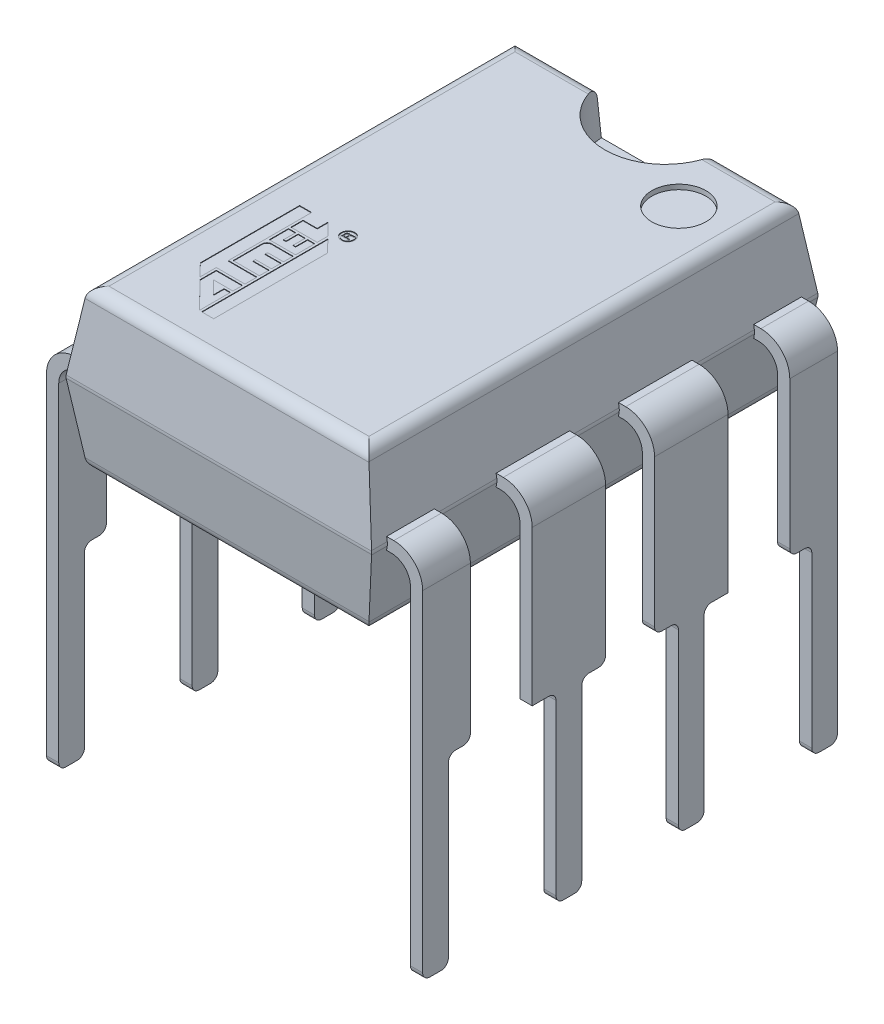
SolidWorks part; units mm, degrees
material "ABS"
ref_plane "Plano frontal" through (0, 0, 0) normal (0, 0, 1) x (1, 0, 0)
ref_plane "Plano superior" through (0, 0, 0) normal (0, 1, 0) x (1, 0, 0)
ref_plane "Plano direito" through (0, 0, 0) normal (1, 0, 0) x (0, 0, -1)
sketch "Esboço1" plane through (0, 0, 0) normal (0, 0, 1) x (1, 0, 0)
  line L0 (-3.175, 0) -> (3.175, 0) construction
  line L1 (3.1687, 0.0393) -> (2.9454, 1.4403)
  line L2 (2.6986, 1.651) -> (-2.6986, 1.651)
  line L3 (-2.9454, 1.4403) -> (-3.1687, 0.0393)
  line L4 (-3.1687, -0.0393) -> (-2.9454, -1.4403)
  line L5 (-2.6986, -1.651) -> (2.6986, -1.651)
  line L6 (3.1687, -0.0393) -> (2.9454, -1.4403)
  line L7 (-2.9119, -1.651) -> (-2.9119, 1.651) construction
  line L8 (2.9119, 1.651) -> (2.9119, -1.651) construction
  line L9 (2.9119, -1.651) -> (-2.9119, 1.651) construction
  line L10 (-2.9119, -1.651) -> (2.9119, 1.651) construction
  arc A0 (-2.6986, 1.651) -> (-2.9454, 1.4403) centre (-2.6986, 1.401) ccw
  arc A1 (-3.1687, -0.0393) -> (-3.1687, 0.0393) centre (-2.9218, 0) cw
  arc A2 (-2.9454, -1.4403) -> (-2.6986, -1.651) centre (-2.6986, -1.401) ccw
  arc A3 (2.6986, -1.651) -> (2.9454, -1.4403) centre (2.6986, -1.401) ccw
  arc A4 (3.1687, -0.0393) -> (3.1687, 0.0393) centre (2.9218, 0) ccw
  arc A5 (2.9454, 1.4403) -> (2.6986, 1.651) centre (2.6986, 1.401) ccw
  dimension "D3" = 0.25
  dimension "D1" = 6.35
  dimension "D2" = 3.302
  dimension "D4" = 5.8238
extrude "Ressalto-extrusão1" add sketch "Esboço1" along normal mid plane 9.271
sketch "Esboço2" plane through (0, 0, 0) normal (1, 0, 0) x (0, 0, -1)
  line L0 (0, 0) -> (6.8137, 0) construction
  line L1 (4.6319, 0.0301) -> (4.4621, 1.4311)
  line L2 (4.6355, -0.0393) -> (4.6355, 0.0393) construction
  line L3 (-4.6355, 1.651) -> (4.6355, 1.651) construction
  line L4 (4.214, 1.651) -> (3.6184, 1.651)
  line L5 (-4.6355, -1.651) -> (4.6355, -1.651) construction
  line L6 (4.4621, -1.4311) -> (4.6319, -0.0301)
  line L7 (3.6184, -1.651) -> (4.214, -1.651)
  line L8 (4.4355, 1.651) -> (5.0977, 1.651)
  line L9 (5.0977, 1.651) -> (5.0977, -1.651)
  line L10 (5.0977, -1.651) -> (4.4355, -1.651)
  line L11 (3.6184, 1.651) -> (3.6184, -1.651)
  line L13 (3.6184, 1.651) -> (5.0977, 1.651)
  line L14 (3.6184, 1.651) -> (3.6184, -1.651)
  line L15 (3.6184, -1.651) -> (5.0977, -1.651)
  line L16 (5.0977, 1.651) -> (5.0977, -1.651)
  arc A0 (4.4621, 1.4311) -> (4.214, 1.651) centre (4.214, 1.401) ccw
  arc A1 (4.6319, 0.0301) -> (4.6319, -0.0301) centre (4.3837, 0) cw
  arc A2 (4.214, -1.651) -> (4.4621, -1.4311) centre (4.214, -1.401) ccw
  point P20 (4.6355, 0)
  dimension "D1" = 0.25
  dimension "D2" = 0.6622
extrude "Corte-extrusão1" cut sketch "Esboço2" against normal through all both and the other way through all contours A1 L0 L9 L8 L13 A0 L1 | L0 A1 L6 A2 L15 L10 L16 region at (0, 0.8822, -4.8091) region at (0, -0.8822, -4.8091)
mirror "Espelhar1" about plane through (0, 0, 0) normal (0, 0, 1) of "Corte-extrusão1"
ref_plane "Plano1" through (0, 0, 1.27) normal (0, 0, 1) x (1, 0, 0)
sketch "Esboço3" plane through (0, 0, 1.27) normal (0, 0, 1) x (1, 0, 0)
  line L0 (-3.904, -7.495) -> (-3.904, -0.475)
  line L1 (-3.304, 0.125) -> (3.304, 0.125)
  line L2 (3.904, -0.475) -> (3.904, -7.495)
  line L3 (3.904, -7.495) -> (3.65, -7.495)
  line L4 (3.65, -7.495) -> (3.65, -0.525)
  line L5 (3.25, -0.125) -> (-3.25, -0.125)
  line L6 (-3.65, -0.525) -> (-3.65, -7.495)
  line L7 (-3.65, -7.495) -> (-3.904, -7.495)
  line L8 (0, -0.125) -> (0, 0.125) construction
  arc A0 (3.65, -0.525) -> (3.25, -0.125) centre (3.25, -0.525) ccw
  arc A1 (-3.25, -0.125) -> (-3.65, -0.525) centre (-3.25, -0.525) ccw
  arc A2 (3.304, 0.125) -> (3.904, -0.475) centre (3.304, -0.475) cw
  arc A3 (-3.904, -0.475) -> (-3.304, 0.125) centre (-3.304, -0.475) cw
  point P17 (3.904, 0.125)
  dimension "D5" = 0.4
  dimension "D6" = 0.6
  dimension "D1" = 0.254
  dimension "D2" = 0.25
  dimension "D3" = 7.3
  dimension "D4" = 7.62
extrude "Ressalto-extrusão2" add sketch "Esboço3" along normal mid plane 1.524
ref_plane "Plano2" through (0, 0, 3.81) normal (0, 0, 1) x (1, 0, 0)
sketch "Esboço4" plane through (0, 0, 3.81) normal (0, 0, 1) x (1, 0, 0)
  line L0 (3.1687, -0.0393) -> (3.1551, -0.125) construction
  line L1 (3.1551, -0.125) -> (3.25, -0.125) construction
  line L2 (3.65, -0.525) -> (3.65, -7.495) construction
  line L3 (3.65, -7.495) -> (3.904, -7.495) construction
  line L4 (3.904, -7.495) -> (3.904, -0.475) construction
  line L5 (3.304, 0.125) -> (3.1551, 0.125) construction
  line L6 (3.1551, 0.125) -> (3.1687, 0.0393) construction
  line L7 (-3.1687, 0.0393) -> (-3.1551, 0.125) construction
  line L8 (-3.1551, 0.125) -> (-3.304, 0.125) construction
  line L9 (-3.904, -0.475) -> (-3.904, -7.495) construction
  line L10 (-3.904, -7.495) -> (-3.65, -7.495) construction
  line L11 (-3.65, -7.495) -> (-3.65, -0.525) construction
  line L12 (-3.25, -0.125) -> (-3.1551, -0.125) construction
  line L13 (-3.1551, -0.125) -> (-3.1687, -0.0393) construction
  line L14 (3.1687, -0.0393) -> (3.1551, -0.125)
  line L15 (3.1551, -0.125) -> (3.25, -0.125)
  line L16 (3.65, -0.525) -> (3.65, -7.495)
  line L17 (3.65, -7.495) -> (3.904, -7.495)
  line L18 (3.904, -7.495) -> (3.904, -0.475)
  line L19 (3.304, 0.125) -> (3.1551, 0.125)
  line L20 (3.1551, 0.125) -> (3.1687, 0.0393)
  line L21 (-3.1687, 0.0393) -> (-3.1551, 0.125)
  line L22 (-3.1551, 0.125) -> (-3.304, 0.125)
  line L23 (-3.904, -0.475) -> (-3.904, -7.495)
  line L24 (-3.904, -7.495) -> (-3.65, -7.495)
  line L25 (-3.65, -7.495) -> (-3.65, -0.525)
  line L26 (-3.25, -0.125) -> (-3.1551, -0.125)
  line L27 (-3.1551, -0.125) -> (-3.1687, -0.0393)
  arc A0 (3.1687, -0.0393) -> (3.1687, 0.0393) centre (2.9218, 0) ccw construction
  arc A1 (3.65, -0.525) -> (3.25, -0.125) centre (3.25, -0.525) ccw construction
  arc A2 (3.904, -0.475) -> (3.304, 0.125) centre (3.304, -0.475) ccw construction
  arc A3 (-3.1687, 0.0393) -> (-3.1687, -0.0393) centre (-2.9218, 0) ccw construction
  arc A4 (-3.304, 0.125) -> (-3.904, -0.475) centre (-3.304, -0.475) ccw construction
  arc A5 (-3.25, -0.125) -> (-3.65, -0.525) centre (-3.25, -0.525) ccw construction
  arc A6 (3.1687, -0.0393) -> (3.1687, 0.0393) centre (2.9218, 0) ccw
  arc A7 (3.65, -0.525) -> (3.25, -0.125) centre (3.25, -0.525) ccw
  arc A8 (3.904, -0.475) -> (3.304, 0.125) centre (3.304, -0.475) ccw
  arc A9 (-3.1687, 0.0393) -> (-3.1687, -0.0393) centre (-2.9218, 0) ccw
  arc A10 (-3.304, 0.125) -> (-3.904, -0.475) centre (-3.304, -0.475) ccw
  arc A11 (-3.25, -0.125) -> (-3.65, -0.525) centre (-3.25, -0.525) ccw
extrude "Ressalto-extrusão3" add sketch "Esboço4" along normal mid plane 0.9906
mirror "Espelhar2" about plane through (0, 0, 0) normal (0, 0, 1) of "Ressalto-extrusão2", "Ressalto-extrusão3"
sketch "Esboço5" plane through (0, 0, 0) normal (1, 0, 0) x (0, 0, -1)
  line L0 (1.882, -3.683) -> (1.6867, -3.683)
  line L1 (2.032, -7.495) -> (2.032, -0.475) construction
  line L2 (1.5367, -3.833) -> (1.5367, -7.345)
  line L3 (2.032, -7.495) -> (0.508, -7.495) construction
  line L4 (1.3867, -7.495) -> (1.1533, -7.495)
  line L5 (1.0033, -7.345) -> (1.0033, -3.833)
  line L6 (0.8533, -3.683) -> (0.658, -3.683)
  line L7 (0.508, -7.495) -> (0.508, -0.475) construction
  line L8 (0.508, -3.683) -> (0.508, -7.7594)
  line L9 (0.508, -7.7594) -> (2.032, -7.7594)
  line L10 (2.032, -7.7594) -> (2.032, -3.683)
  line L11 (2.032, -3.683) -> (1.5367, -3.683)
  line L12 (-4.214, 1.651) -> (4.214, 1.651) construction
  line L13 (3.4647, -3.683) -> (3.6219, -3.683)
  line L14 (3.3147, -7.495) -> (3.3147, -0.475) construction
  line L15 (3.7719, -3.833) -> (3.7719, -7.345)
  line L16 (4.3053, -7.495) -> (3.3147, -7.495) construction
  line L17 (3.9219, -7.495) -> (4.1553, -7.495)
  line L18 (4.3053, -7.495) -> (4.3053, -7.9729)
  line L19 (4.3053, -7.9729) -> (3.3147, -7.9729)
  line L20 (3.3147, -7.9729) -> (3.3147, -3.683)
  line L21 (0.508, -3.533) -> (0.508, -2.7844)
  line L22 (0.508, -2.7844) -> (-0.1796, -2.7844)
  line L23 (-0.1796, -2.7844) -> (-0.1796, -7.8443)
  line L24 (-0.1796, -7.8443) -> (-0.0892, -7.8443)
  line L25 (-0.1796, -7.8443) -> (0.508, -7.7594)
  line L26 (2.032, -2.7844) -> (2.622, -2.7844)
  line L27 (2.622, -2.7844) -> (2.622, -7.495)
  line L28 (2.622, -7.495) -> (2.032, -7.495)
  line L29 (3.3147, -3.533) -> (3.3147, -2.7844)
  line L30 (3.3147, -2.7844) -> (3.0353, -2.7844)
  line L31 (3.0353, -2.7844) -> (3.0353, -7.8443)
  line L32 (3.0353, -7.8443) -> (3.3147, -7.9729)
  line L33 (2.032, -3.533) -> (2.032, -2.7844)
  line L34 (2.032, -2.7844) -> (2.0505, -2.7728)
  line L35 (3.3147, -3.683) -> (3.3147, -2.7844)
  line L36 (4.3053, -7.345) -> (4.3053, -7.2012)
  line L37 (4.3053, -7.495) -> (4.3053, -0.475) construction
  line L38 (4.3053, -7.2012) -> (4.8161, -7.2012)
  line L39 (4.8161, -7.2012) -> (4.3053, -7.9729)
  arc A0 (1.1533, -7.495) -> (1.0033, -7.345) centre (1.1533, -7.345) cw
  arc A1 (1.5367, -7.345) -> (1.3867, -7.495) centre (1.3867, -7.345) cw
  arc A2 (3.7719, -7.345) -> (3.9219, -7.495) centre (3.9219, -7.345) ccw
  arc A3 (3.6219, -3.683) -> (3.7719, -3.833) centre (3.6219, -3.833) cw
  arc A4 (3.4647, -3.683) -> (3.3147, -3.533) centre (3.4647, -3.533) cw
  arc A5 (2.032, -3.533) -> (1.882, -3.683) centre (1.882, -3.533) cw
  arc A6 (1.6867, -3.683) -> (1.5367, -3.833) centre (1.6867, -3.833) ccw
  arc A7 (0.8533, -3.683) -> (1.0033, -3.833) centre (0.8533, -3.833) cw
  arc A8 (0.508, -3.533) -> (0.658, -3.683) centre (0.658, -3.533) ccw
  arc A9 (4.1553, -7.495) -> (4.3053, -7.345) centre (4.1553, -7.345) ccw
  point P42 (1.0033, -7.495)
  point P45 (1.5367, -7.495)
  point P48 (3.7719, -7.495)
  point P56 (2.032, -3.683)
  dimension "D3" = 0.15
  dimension "D4" = 0.15
  dimension "D5" = 0.15
  dimension "D6" = 0.15
  dimension "D7" = 0.15
  dimension "D8" = 0.15
  dimension "D9" = 0.15
  dimension "D10" = 0.15
  dimension "D11" = 0.15
  dimension "D12" = 0.15
  dimension "D1" = 5.334
  dimension "D2" = 0.5334
extrude "Corte-extrusão3" cut sketch "Esboço5" against normal through all both and the other way through all contours L9 L10 L0 L2 L4 L5 L6 L8 | L20 L19 L18 L17 L15 L13 region at (0, -5.5664, -0.7693) region at (0, -6.1675, -3.6724)
mirror "Espelhar3" about plane through (0, 0, 0) normal (0, 0, 1) of "Corte-extrusão3"
sketch "Esboço7" plane through (0, 1.651, 0) normal (0, 1, 0) x (1, 0, 0)
  line L0 (-3.17, 4.6319) -> (3.17, 4.6319) construction
  line L1 (1.25, 4.6319) -> (-1.25, 4.6319)
  arc A0 (-1.25, 4.6319) -> (1.25, 4.6319) centre (0, 4.6319) ccw
  dimension "D1" = 2.5
extrude "Corte-extrusão4" cut sketch "Esboço7" against normal blind 0.9906
sketch "Esboço8" plane through (0, 1.651, 0) normal (0, 1, 0) x (1, 0, 0)
  line L0 (-1.0257, -3.7127) -> (-1.3257, -3.7127)
  line L1 (-1.3257, -3.7127) -> (-2.17, -2.8467)
  line L2 (-2.17, -2.8467) -> (-2.17, -0.484)
  line L3 (-2.17, -0.484) -> (-1.3257, -0.484)
  line L4 (-1.3257, -0.484) -> (-1.0257, -0.7917)
  line L5 (-1.0257, -0.7917) -> (-1.0257, -3.7127)
  line L6 (-1.5757, -0.7858) -> (-2.17, -0.7858)
  line L7 (-1.3257, -3.7127) -> (-1.3257, -0.484) construction
  line L8 (-1.92, -0.484) -> (-1.92, -2.5145)
  line L9 (-1.92, -2.5145) -> (-1.3257, -2.5145)
  line L10 (-1.92, -2.7645) -> (-1.92, -3.1031)
  line L11 (-1.92, -2.7645) -> (-1.3257, -2.7645)
  line L12 (-1.3257, -2.4645) -> (-1.87, -2.4645)
  line L13 (-1.87, -2.4645) -> (-1.87, -1.8645)
  line L14 (-1.77, -1.7645) -> (-1.3257, -1.7645)
  line L15 (-1.3257, -1.7645) -> (-1.3257, -1.9645)
  line L16 (-1.3257, -1.9645) -> (-1.636, -1.9645)
  line L17 (-1.656, -1.9845) -> (-1.656, -2.0145)
  line L18 (-1.656, -2.0145) -> (-1.3257, -2.0145)
  line L19 (-1.3257, -2.0145) -> (-1.3257, -2.2145)
  line L20 (-1.3257, -2.2145) -> (-1.656, -2.2145)
  line L21 (-1.656, -2.2145) -> (-1.656, -2.2645)
  line L22 (-1.656, -2.2645) -> (-1.3257, -2.2645)
  line L23 (-1.87, -1.3145) -> (-1.87, -1.7145)
  line L24 (-1.87, -1.7145) -> (-1.3257, -1.7145)
  line L25 (-1.3257, -1.7145) -> (-1.3257, -1.3145)
  line L26 (-1.5238, -1.3145) -> (-1.6719, -1.3145)
  line L27 (-1.5238, -1.3145) -> (-1.5238, -1.5645)
  line L28 (-1.5238, -1.5645) -> (-1.4738, -1.5645)
  line L29 (-1.4738, -1.5645) -> (-1.4738, -1.3145)
  line L30 (-1.2757, -3.7127) -> (-1.2757, -1.0936)
  line L31 (-1.6719, -1.3145) -> (-1.6719, -1.5645)
  line L32 (-1.6719, -1.5645) -> (-1.7219, -1.5645)
  line L33 (-1.7219, -1.5645) -> (-1.7219, -1.3145)
  line L34 (-1.7219, -1.3145) -> (-1.87, -1.3145)
  line L35 (-1.0257, -1.35) -> (-1.87, -0.484)
  line L36 (-1.87, -1.2645) -> (-1.87, -1.0145)
  line L37 (-1.87, -1.0145) -> (-1.5757, -1.0145)
  line L38 (-1.5757, -1.0145) -> (-1.5757, -0.7858)
  line L39 (-1.87, -1.2645) -> (-1.3257, -1.2645)
  line L40 (-1.3257, -3.709) -> (-1.87, -3.1507)
  line L41 (-1.87, -3.1507) -> (-1.87, -2.8145)
  line L42 (-1.87, -2.8145) -> (-1.3257, -2.8145)
  line L43 (-1.3257, -2.8145) -> (-1.3257, -3.0145)
  line L44 (-1.3257, -3.0145) -> (-1.7234, -3.0145)
  line L45 (-1.7234, -3.0145) -> (-1.4583, -3.2865)
  line L46 (-1.4583, -3.2865) -> (-1.4583, -3.0645)
  line L47 (-1.4583, -3.0645) -> (-1.3257, -3.0645)
  line L48 (-1.3257, -1.3145) -> (-1.4738, -1.3145)
  line L49 (-1.3257, -3.709) -> (-1.3257, -3.0645)
  line L50 (-1.3257, -3.0145) -> (-1.3257, -2.8145)
  line L51 (-1.3257, -2.7645) -> (-1.3257, -2.5145)
  line L52 (-1.3257, -2.4645) -> (-1.3257, -2.2645)
  line L53 (-1.3257, -1.9645) -> (-1.3257, -2.4202)
  line L54 (-1.3257, -1.2645) -> (-1.3257, -1.0423)
  arc A0 (-1.87, -1.8645) -> (-1.77, -1.7645) centre (-1.77, -1.8645) cw
  arc A1 (-1.636, -1.9645) -> (-1.656, -1.9845) centre (-1.636, -1.9845) ccw
  point P60 (-1.87, -1.7645)
  point P63 (-1.656, -1.9645)
  dimension "D20" = 0.1
  dimension "D21" = 0.02
  dimension "D1" = 0.25
  dimension "D2" = 0.25
  dimension "D3" = 0.25
  dimension "D4" = 0.25
  dimension "D5" = 0.2
  dimension "D6" = 0.05
  dimension "D7" = 0.05
  dimension "D8" = 0.25
  dimension "D9" = 3.2288
  dimension "D10" = 0.05
  dimension "D11" = 0.05
  dimension "D12" = 0.05
  dimension "D13" = 0.05
  dimension "D14" = 0.2
  dimension "D15" = 0.05
  dimension "D16" = 0.05
  dimension "D17" = 0.05
  dimension "D18" = 0.2
  dimension "D19" = 0.25
  dimension "D22" = 0.05
  dimension "D23" = 0.4
extrude "Corte-extrusão5" cut sketch "Esboço8" against normal blind 0.01 contours L5 L35 L30 L0 | L40 L49 L47 L46 L45 L44 L43 L42 L41 | L11 L51 L9 L8 L3 L2 L1 L10 | A1 L16 L15 L14 A0 L13 L12 L52 L22 L21 L20 L19 L18 L17 | L25 L48 L29 L28 L27 L26 L31 L32 L33 L34 L23 L24 | L39 L54 L35 L38 L37 L36 region at (-1.1529, 1.651, 2.4662) region at (-1.953, 1.651, 2.0434) region at (-1.5832, 1.651, 1.108) region at (-1.6066, 1.651, 2.1165) region at (-1.5979, 1.651, 1.5243) region at (-1.5904, 1.651, 3.4226)
sketch "Esboço9" plane through (0, 1.651, 0) normal (0, 1, 0) x (1, 0, 0)
  text T0 "<r90> ®</r>" font "Century Gothic" height in points 1
extrude "Corte-extrusão6" cut sketch "Esboço9" against normal blind 0.01
sketch "Esboço10" plane through (0, 1.651, 0) normal (0, 1, 0) x (1, 0, 0)
  circle A0 centre (1.7786, 3.1382) radius 0.5614
extrude "Corte-extrusão7" cut sketch "Esboço10" against normal blind 0.1
